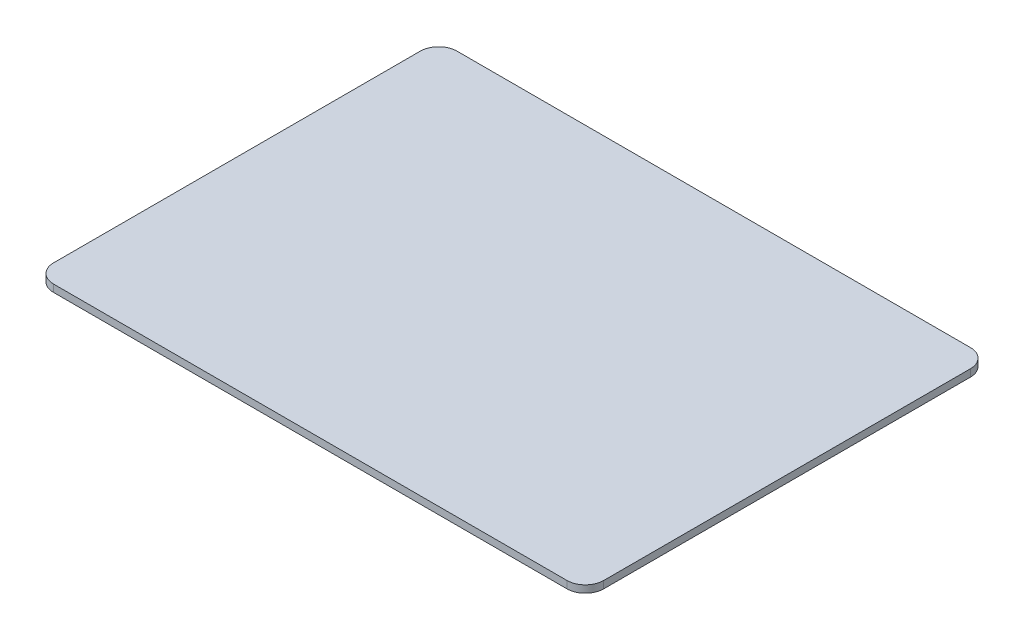
SolidWorks part; units mm, degrees
material "Neoprene Rubber"
ref_plane "Front Plane" through (0, 0, 0) normal (0, 0, 1) x (1, 0, 0)
ref_plane "Top Plane" through (0, 0, 0) normal (0, 1, 0) x (1, 0, 0)
ref_plane "Right Plane" through (0, 0, 0) normal (1, 0, 0) x (0, 0, -1)
ref_axis "Axis1" through (0, 0, -88.99) along (0, 0, 1)
ref_axis "Axis2" through (0, -55, 0) along (0, 1, 0)
ref_axis "Axis3" through (-88.99, 0, 0) along (1, 0, 0)
sketch "Sketch1" plane through (0, 0, 0) normal (0, 1, 0) x (1, 0, 0)
  line L1 (28, -22) -> (-28, -22)
  line L2 (30, -20) -> (30, 20)
  line L3 (28, 22) -> (-28, 22)
  line L4 (-30, -20) -> (-30, 20)
  line L5 (30, -22) -> (-30, 22) construction
  line L6 (30, 22) -> (-30, -22) construction
  arc A0 (30, 20) -> (28, 22) centre (28, 20) ccw
  arc A1 (28, -22) -> (30, -20) centre (28, -20) ccw
  arc A2 (-28, -22) -> (-30, -20) centre (-28, -20) cw
  arc A3 (-28, 22) -> (-30, 20) centre (-28, 20) ccw
  point P0 (0, 0)
  dimension "D3" = 2
  dimension "D1" = 44
  dimension "D2" = 60
extrude "Boss-Extrude1" add sketch "Sketch1" along normal blind 0.7937
